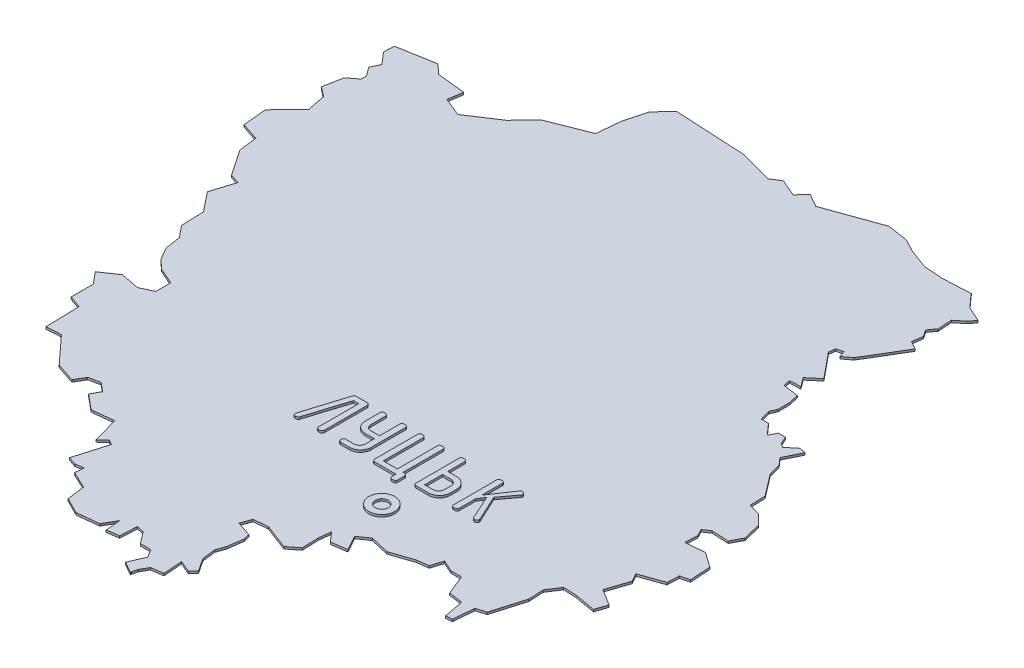
SolidWorks part; units mm, degrees
ref_plane "Спереди" through (0, 0, 0) normal (0, 0, 1) x (1, 0, 0)
ref_plane "Сверху" through (0, 0, 0) normal (0, 1, 0) x (1, 0, 0)
ref_plane "Справа" through (0, 0, 0) normal (1, 0, 0) x (0, 0, -1)
sketch "Эскиз1" plane through (0, 0, 0) normal (0, 1, 0) x (1, 0, 0)
  line B0 (-8480.3259, 8945.7632) -> (-8524.4635, 8941.8693)
  line B1 (-8524.4635, 8941.8693) -> (-8523.1427, 8971.0692)
  line B2 (-8523.1427, 8971.0692) -> (-8531.5781, 8986.6546)
  line B3 (-8531.5781, 8986.6546) -> (-8516.0028, 8997.0229)
  line B4 (-8516.0028, 8997.0229) -> (-8477.0976, 8995.0722)
  line B5 (-8477.0976, 8995.0722) -> (-8463.4527, 9020.3909)
  line B6 (-8463.4527, 9020.3909) -> (-8473.186, 9061.2874)
  line B7 (-8473.186, 9061.2874) -> (-8497.1992, 9085.2904)
  line B8 (-8497.1992, 9085.2904) -> (-8523.1427, 9092.4177)
  line B9 (-8523.1427, 9092.4177) -> (-8524.4635, 9128.125)
  line B10 (-8524.4635, 9128.125) -> (-8562.0733, 9177.4315)
  line B11 (-8562.0733, 9177.4315) -> (-8570.534, 9206.6415)
  line B12 (-8570.534, 9206.6415) -> (-8584.1535, 9222.1964)
  line B13 (-8584.1535, 9222.1964) -> (-8565.3499, 9261.1524)
  line B14 (-8565.3499, 9261.1524) -> (-8579.6044, 9264.4011)
  line B15 (-8579.6044, 9264.4011) -> (-8601.6668, 9246.2223)
  line B16 (-8601.6668, 9246.2223) -> (-8611.4153, 9252.7095)
  line B17 (-8611.4153, 9252.7095) -> (-8618.5527, 9269.5776)
  line B18 (-8618.5527, 9269.5776) -> (-8635.4183, 9269.5776)
  line B19 (-8635.4183, 9269.5776) -> (-8643.8588, 9252.7095)
  line B20 (-8643.8588, 9252.7095) -> (-8666.5765, 9278.0155)
  line B21 (-8666.5765, 9278.0155) -> (-8683.432, 9278.0155)
  line B22 (-8683.432, 9278.0155) -> (-8683.432, 9278.653)
  line B23 (-8683.432, 9278.653) -> (-8689.9293, 9302.0261)
  line B24 (-8689.9293, 9302.0261) -> (-8683.432, 9316.9715)
  line B25 (-8683.432, 9316.9715) -> (-8683.432, 9342.2775)
  line B26 (-8683.432, 9342.2775) -> (-8688.639, 9366.9282)
  line B27 (-8688.639, 9366.9282) -> (-8724.3234, 9372.125)
  line B28 (-8724.3234, 9372.125) -> (-8727.5721, 9387.6825)
  line B29 (-8727.5721, 9387.6825) -> (-8702.261, 9388.983)
  line B30 (-8702.261, 9388.983) -> (-8717.8388, 9409.7627)
  line B31 (-8717.8388, 9409.7627) -> (-8691.8825, 9431.8252)
  line B32 (-8691.8825, 9431.8252) -> (-8739.9139, 9490.2223)
  line B33 (-8739.9139, 9490.2223) -> (-8737.9581, 9505.1397)
  line B34 (-8737.9581, 9505.1397) -> (-8722.3727, 9509.031)
  line B35 (-8722.3727, 9509.031) -> (-8717.8388, 9494.7562)
  line B36 (-8717.8388, 9494.7562) -> (-8699.0047, 9509.031)
  line B37 (-8699.0047, 9509.031) -> (-8683.432, 9534.3624)
  line B38 (-8683.432, 9534.3624) -> (-8645.8095, 9597.3011)
  line B39 (-8645.8095, 9597.3011) -> (-8664.6258, 9607.677)
  line B40 (-8664.6258, 9607.677) -> (-8661.3644, 9631.6851)
  line B41 (-8661.3644, 9631.6851) -> (-8671.7607, 9647.2654)
  line B42 (-8671.7607, 9647.2654) -> (-8659.4213, 9664.126)
  line B43 (-8659.4213, 9664.126) -> (-8661.3644, 9696.5745)
  line B44 (-8661.3644, 9696.5745) -> (-8640.6203, 9713.4553)
  line B45 (-8640.6203, 9713.4553) -> (-8630.2139, 9727.0875)
  line B46 (-8630.2139, 9727.0875) -> (-8664.6258, 9742.6678)
  line B47 (-8664.6258, 9742.6678) -> (-8683.432, 9763.4425)
  line B48 (-8683.432, 9763.4425) -> (-8691.8825, 9773.1605)
  line B49 (-8691.8825, 9773.1605) -> (-8756.7541, 9769.9144)
  line B50 (-8756.7541, 9769.9144) -> (-8799.5912, 9773.1605)
  line B51 (-8799.5912, 9773.1605) -> (-8845.6643, 9790.0185)
  line B52 (-8845.6643, 9790.0185) -> (-8874.2266, 9805.6014)
  line B53 (-8874.2266, 9805.6014) -> (-8922.2402, 9812.7464)
  line B54 (-8922.2402, 9812.7464) -> (-9046.8475, 9767.9612)
  line B55 (-9046.8475, 9767.9612) -> (-9077.3479, 9785.4973)
  line B56 (-9077.3479, 9785.4973) -> (-9096.1667, 9764.7303)
  line B57 (-9096.1667, 9764.7303) -> (-9135.7475, 9781.6086)
  line B58 (-9135.7475, 9781.6086) -> (-9157.81, 9767.9612)
  line B59 (-9157.81, 9767.9612) -> (-9234.3884, 9788.7206)
  line B60 (-9234.3884, 9788.7206) -> (-9299.288, 9791.9692)
  line B61 (-9299.288, 9791.9692) -> (-9398.569, 9797.1661)
  line B62 (-9398.569, 9797.1661) -> (-9429.0769, 9764.7303)
  line B63 (-9429.0769, 9764.7303) -> (-9442.6862, 9713.4553)
  line B64 (-9442.6862, 9713.4553) -> (-9447.8805, 9658.9418)
  line B65 (-9447.8805, 9658.9418) -> (-9538.7287, 9623.2574)
  line B66 (-9538.7287, 9623.2574) -> (-9577.6872, 9582.3761)
  line B67 (-9577.6872, 9582.3761) -> (-9645.8253, 9537.5857)
  line B68 (-9645.8253, 9537.5857) -> (-9688.6497, 9555.1193)
  line B69 (-9688.6497, 9555.1193) -> (-9683.4477, 9588.8556)
  line B70 (-9683.4477, 9588.8556) -> (-9748.3371, 9596.0006)
  line B71 (-9748.3371, 9596.0006) -> (-9770.4072, 9616.12)
  line B72 (-9770.4072, 9616.12) -> (-9856.0738, 9601.1797)
  line B73 (-9856.0738, 9601.1797) -> (-9857.3565, 9577.1741)
  line B74 (-9857.3565, 9577.1741) -> (-9834.0189, 9549.9276)
  line B75 (-9834.0189, 9549.9276) -> (-9843.7344, 9529.158)
  line B76 (-9843.7344, 9529.158) -> (-9828.8069, 9509.031)
  line B77 (-9828.8069, 9509.031) -> (-9828.8069, 9496.7146)
  line B78 (-9828.8069, 9496.7146) -> (-9850.8718, 9479.8413)
  line B79 (-9850.8718, 9479.8413) -> (-9859.3123, 9435.0637)
  line B80 (-9859.3123, 9435.0637) -> (-9837.2422, 9418.1828)
  line B81 (-9837.2422, 9418.1828) -> (-9828.8069, 9375.3661)
  line B82 (-9828.8069, 9375.3661) -> (-9878.1286, 9324.0962)
  line B83 (-9878.1286, 9324.0962) -> (-9872.9394, 9269.5776)
  line B84 (-9872.9394, 9269.5776) -> (-9832.0606, 9255.9708)
  line B85 (-9832.0606, 9255.9708) -> (-9826.8638, 9213.7738)
  line B86 (-9826.8638, 9213.7738) -> (-9785.985, 9153.4158)
  line B87 (-9785.985, 9153.4158) -> (-9763.92, 9146.9362)
  line B88 (-9763.92, 9146.9362) -> (-9780.7805, 9092.4177)
  line B89 (-9780.7805, 9092.4177) -> (-9745.0859, 9047.6502)
  line B90 (-9745.0859, 9047.6502) -> (-9743.1682, 8995.0722)
  line B91 (-9743.1682, 8995.0722) -> (-9721.088, 8967.8231)
  line B92 (-9721.088, 8967.8231) -> (-9715.8912, 8932.1284)
  line B93 (-9715.8912, 8932.1284) -> (-9699.0306, 8902.9337)
  line B94 (-9699.0306, 8902.9337) -> (-9678.2458, 8884.1199)
  line B95 (-9678.2458, 8884.1199) -> (-9640.6081, 8867.2492)
  line B96 (-9640.6081, 8867.2492) -> (-9640.6081, 8832.8373)
  line B97 (-9640.6081, 8832.8373) -> (-9669.8257, 8819.228)
  line B98 (-9669.8257, 8819.228) -> (-9712.6476, 8827.6608)
  line B99 (-9712.6476, 8827.6608) -> (-9750.2878, 8802.3471)
  line B100 (-9750.2878, 8802.3471) -> (-9727.5802, 8775.1056)
  line B101 (-9727.5802, 8775.1056) -> (-9727.5802, 8723.8307)
  line B102 (-9727.5802, 8723.8307) -> (-9699.0306, 8713.4497)
  line B103 (-9699.0306, 8713.4497) -> (-9697.0723, 8634.9205)
  line B104 (-9697.0723, 8634.9205) -> (-9663.3182, 8636.8738)
  line B105 (-9663.3182, 8636.8738) -> (-9604.9236, 8573.2747)
  line B106 (-9604.9236, 8573.2747) -> (-9560.8064, 8558.3497)
  line B107 (-9560.8064, 8558.3497) -> (-9547.1717, 8581.7151)
  line B108 (-9547.1717, 8581.7151) -> (-9521.2281, 8586.9069)
  line B109 (-9521.2281, 8586.9069) -> (-9501.1011, 8570.0337)
  line B110 (-9501.1011, 8570.0337) -> (-9512.7801, 8549.2717)
  line B111 (-9512.7801, 8549.2717) -> (-9478.3935, 8520.7119)
  line B112 (-9478.3935, 8520.7119) -> (-9429.0769, 8525.9037)
  line B113 (-9429.0769, 8525.9037) -> (-9412.191, 8466.1985)
  line B114 (-9412.191, 8466.1985) -> (-9396.6386, 8481.1235)
  line B115 (-9396.6386, 8481.1235) -> (-9384.9342, 8474.6287)
  line B116 (-9384.9342, 8474.6287) -> (-9407.0068, 8399.3584)
  line B117 (-9407.0068, 8399.3584) -> (-9388.188, 8392.8788)
  line B118 (-9388.188, 8392.8788) -> (-9369.3742, 8396.1122)
  line B119 (-9369.3742, 8396.1122) -> (-9371.3097, 8375.3452)
  line B120 (-9371.3097, 8375.3452) -> (-9331.7314, 8356.5314)
  line B121 (-9331.7314, 8356.5314) -> (-9326.5422, 8315.6374)
  line B122 (-9326.5422, 8315.6374) -> (-9289.5522, 8296.8236)
  line B123 (-9289.5522, 8296.8236) -> (-9239.57, 8302.0052)
  line B124 (-9239.57, 8302.0052) -> (-9222.7171, 8331.2279)
  line B125 (-9222.7171, 8331.2279) -> (-9219.4685, 8296.8236)
  line B126 (-9219.4685, 8296.8236) -> (-9192.1889, 8300.7276)
  line B127 (-9192.1889, 8300.7276) -> (-9190.2636, 8339.6607)
  line B128 (-9190.2636, 8339.6607) -> (-9173.398, 8336.4172)
  line B129 (-9173.398, 8336.4172) -> (-9152.6208, 8309.1604)
  line B130 (-9152.6208, 8309.1604) -> (-9128.5949, 8309.1604)
  line B131 (-9128.5949, 8309.1604) -> (-9116.9185, 8290.339)
  line B132 (-9116.9185, 8290.339) -> (-9132.4989, 8254.6419)
  line B133 (-9132.4989, 8254.6419) -> (-9105.2421, 8239.0793)
  line B134 (-9105.2421, 8239.0793) -> (-9106.5452, 8242.3051)
  line B135 (-9106.5452, 8242.3051) -> (-9103.3092, 8254.6419)
  line B136 (-9103.3092, 8254.6419) -> (-9092.9104, 8272.8156)
  line B137 (-9092.9104, 8272.8156) -> (-9065.6613, 8276.7297)
  line B138 (-9065.6613, 8276.7297) -> (-9068.9024, 8320.8444)
  line B139 (-9068.9024, 8320.8444) -> (-9041.6507, 8309.1604)
  line B140 (-9041.6507, 8309.1604) -> (-9029.9845, 8320.8444)
  line B141 (-9029.9845, 8320.8444) -> (-9050.0937, 8351.3295)
  line B142 (-9050.0937, 8351.3295) -> (-9053.9748, 8382.4851)
  line B143 (-9053.9748, 8382.4851) -> (-9046.8475, 8402.6096)
  line B144 (-9046.8475, 8402.6096) -> (-9041.6507, 8438.9443)
  line B145 (-9041.6507, 8438.9443) -> (-9044.8968, 8452.5739)
  line B146 (-9044.8968, 8452.5739) -> (-9079.3113, 8464.2706)
  line B147 (-9079.3113, 8464.2706) -> (-9070.8556, 8488.2584)
  line B148 (-9070.8556, 8488.2584) -> (-9038.3944, 8491.5121)
  line B149 (-9038.3944, 8491.5121) -> (-8980.6501, 8469.4395)
  line B150 (-8980.6501, 8469.4395) -> (-8956.6394, 8488.2584)
  line B151 (-8956.6394, 8488.2584) -> (-8957.9323, 8527.2093)
  line B152 (-8957.9323, 8527.2093) -> (-8954.7014, 8554.4431)
  line B153 (-8954.7014, 8554.4431) -> (-8935.8826, 8532.4036)
  line B154 (-8935.8826, 8532.4036) -> (-8900.1803, 8537.5775)
  line B155 (-8900.1803, 8537.5775) -> (-8919.0068, 8571.9717)
  line B156 (-8919.0068, 8571.9717) -> (-8895.0038, 8588.8424)
  line B157 (-8895.0038, 8588.8424) -> (-8850.8662, 8578.4715)
  line B158 (-8850.8662, 8578.4715) -> (-8799.5912, 8595.9747)
  line B159 (-8799.5912, 8595.9747) -> (-8773.6426, 8599.2437)
  line B160 (-8773.6426, 8599.2437) -> (-8765.2047, 8626.4902)
  line B161 (-8765.2047, 8626.4902) -> (-8737.9581, 8614.1484)
  line B162 (-8737.9581, 8614.1484) -> (-8713.9551, 8614.1484)
  line B163 (-8713.9551, 8614.1484) -> (-8695.116, 8568.0829)
  line B164 (-8695.116, 8568.0829) -> (-8683.432, 8566.7774)
  line B165 (-8683.432, 8566.7774) -> (-8662.6725, 8563.5414)
  line B166 (-8662.6725, 8563.5414) -> (-8654.2423, 8517.4684)
  line B167 (-8654.2423, 8517.4684) -> (-8639.3096, 8518.746)
  line B168 (-8639.3096, 8518.746) -> (-8635.4183, 8566.7774)
  line B169 (-8635.4183, 8566.7774) -> (-8613.3635, 8573.2747)
  line B170 (-8613.3635, 8573.2747) -> (-8591.2858, 8648.5425)
  line B171 (-8591.2858, 8648.5425) -> (-8593.2391, 8682.9417)
  line B172 (-8593.2391, 8682.9417) -> (-8574.4228, 8711.504)
  line B173 (-8574.4228, 8711.504) -> (-8543.2671, 8710.2036)
  line B174 (-8543.2671, 8710.2036) -> (-8495.9012, 8701.7555)
  line B175 (-8495.9012, 8701.7555) -> (-8486.8055, 8729.0173)
  line B176 (-8486.8055, 8729.0173) -> (-8524.4635, 8752.3904)
  line B177 (-8524.4635, 8752.3904) -> (-8507.5649, 8803.6502)
  line B178 (-8507.5649, 8803.6502) -> (-8517.9586, 8822.4639)
  line B179 (-8517.9586, 8822.4639) -> (-8464.7481, 8841.298)
  line B180 (-8464.7481, 8841.298) -> (-8463.4527, 8868.5472)
  line B181 (-8463.4527, 8868.5472) -> (-8442.6679, 8873.7288)
  line B182 (-8442.6679, 8873.7288) -> (-8445.9445, 8921.7475)
  line B183 (-8445.9445, 8921.7475) -> (-8480.3259, 8945.7632)
sketch_block_instance "Блок25-1"
sketch_block "Блок25"
extrude "Бобышка-Вытянуть1" add sketch "Эскиз1" along normal blind 5 contours B182 B183 B0 B1 B2 B3 B4 B5 B6 B7 B8 B9 B10 B11 B12 B13 B14 B15 B16 B17 B18 B19 B20 B21 B22 B23 B24 B25 B26 B27 B28 B29 B30 B31 B32 B33 B34 B35 B36 B37 B38 B39 B40 B41 B42 B43 B44 B45 B46 B47 B48
sketch "Эскиз2" plane through (0, 0, 0) normal (0, 1, 0) x (1, 0, 0)
  line L0 (-9236.356, 8739.4816) -> (-8693.2049, 8739.4816) construction
  circle A0 centre (-8947.3825, 8663.2073) radius 15
  circle A1 centre (-8947.3825, 8663.2073) radius 30
  text T0 "<b>ЛУЦЬК</b>" font "GOST Type AU" height 110
  dimension "D1" = 30
  dimension "D2" = 60
extrude "Бобышка-Вытянуть2" add sketch "Эскиз2" along normal blind 10
scale "Масштаб1" scale about centroid uniform scaling yes scale factor 0.05
